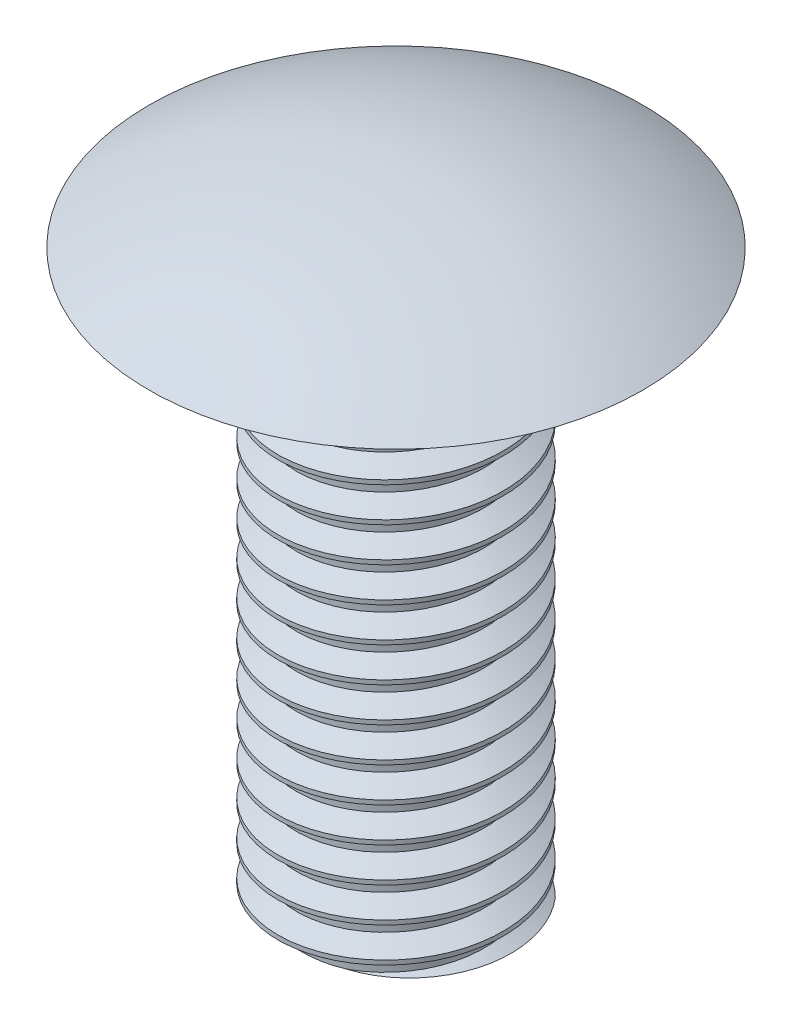
SolidWorks part; units mm, degrees
material "PET"
ref_plane "Front Plane" through (0, 0, 0) normal (0, 0, 1) x (1, 0, 0)
ref_plane "Top Plane" through (0, 0, 0) normal (0, 1, 0) x (1, 0, 0)
ref_plane "Right Plane" through (0, 0, 0) normal (1, 0, 0) x (0, 0, -1)
sketch "Sketch1" plane through (0, 0, 0) normal (0, 0, 1) x (1, 0, 0)
  line L0 (5.0845, 14.0107) -> (12.6548, 14.0107)
  line L2 (-1.2655, 14.0107) -> (-1.2655, -17.7393)
  line L3 (-1.2655, -17.7393) -> (5.0845, -17.7393)
  line L4 (5.0845, 14.0107) -> (5.0845, -17.7393)
  line L5 (-1.2655, 14.0107) -> (-1.2655, 17.8207)
  arc A0 (-1.2655, 17.8207) -> (12.6548, 14.0107) centre (-1.2655, -9.514) cw
  dimension "D1" = 31.75
  dimension "D2" = 6.35
revolve "Revolve1" add sketch "Sketch1" angle 360 about L2
thread "Thread1" pitch 1.9538 method cut profile "Thread Profile1" start angle 0, offset 0, length 0, pitch 1.9538, diameter 12.7
ref_plane "Plane1" through (-7.6155, 14.0107, 0) normal (0, 0, 1) x (-1, 0, 0)
sketch "Thread Profile1" plane through (-7.6155, 14.0107, 0) normal (0, 0, 1) x (-1, 0, 0)
  line L0 (0, 0) -> (0, 1.9538) construction
  line L11 (0, 0) -> (0, 1.7096)
  line L12 (0, 1.7096) -> (-1.0576, 1.099)
  line L13 (-1.0576, 1.099) -> (-1.0576, 0.6106)
  line L15 (-1.0576, 0.6106) -> (0, 0)
  line L17 (-1.0576, 0.8548) -> (0, 0.8548) construction
  point P2 (0, 0)
  dimension "Pitch" = 1.9538
  dimension "Profile_Angle" = 60
  dimension "Profile_Land" = 0.4885
  dimension "Profile_Height" = 1.0576
